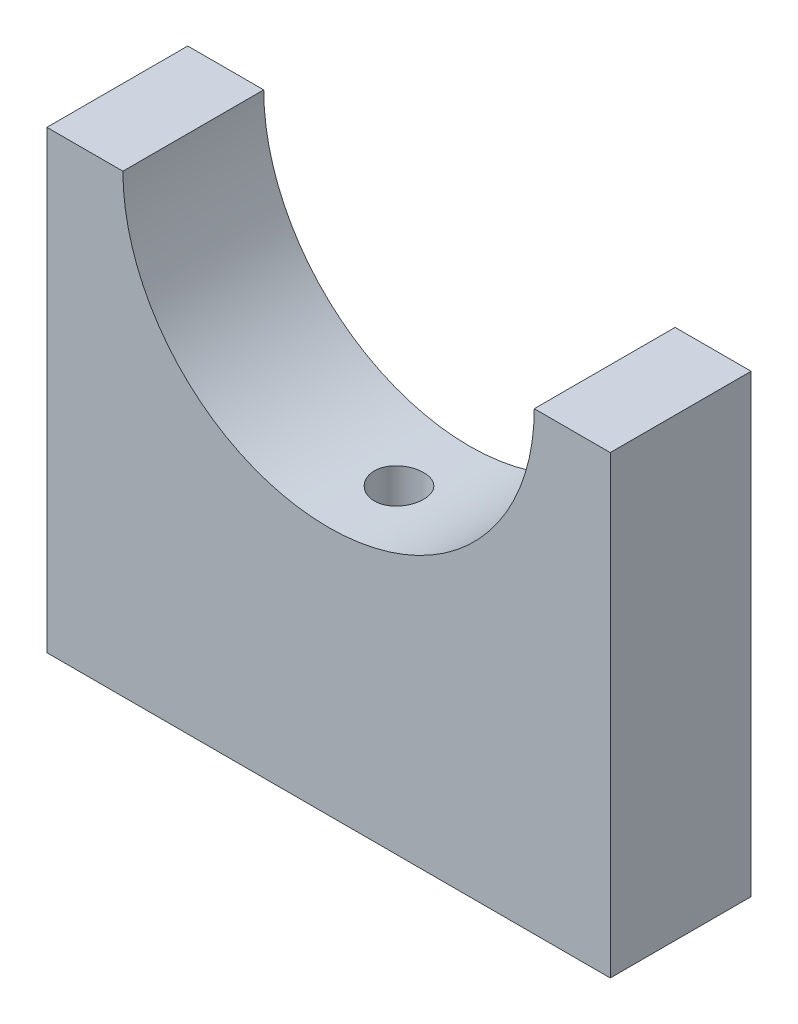
SolidWorks part; units mm, degrees
ref_plane "Front Plane" through (0, 0, 0) normal (0, 0, 1) x (1, 0, 0)
ref_plane "Top Plane" through (0, 0, 0) normal (0, 1, 0) x (1, 0, 0)
ref_plane "Right Plane" through (0, 0, 0) normal (1, 0, 0) x (0, 0, -1)
sketch "Sketch1" plane through (0, 0, 0) normal (0, 0, 1) x (1, 0, 0)
  line L1 (-40, 32.31) -> (40, 32.31)
  line L2 (-40, 32.31) -> (-40, -32.31)
  line L3 (-40, -32.31) -> (40, -32.31)
  line L4 (40, 32.31) -> (40, -32.31)
  line L5 (-40, 32.31) -> (40, -32.31) construction
  line L6 (-40, -32.31) -> (40, 32.31) construction
  point P0 (0, 0)
  dimension "D1" = 64.62
  dimension "D2" = 80
extrude "Boss-Extrude1" add sketch "Sketch1" along normal mid plane 20
sketch "Sketch2" plane through (0, 0, 10) normal (0, 0, 1) x (1, 0, 0)
  line L0 (40, 32.31) -> (-40, 32.31) construction
  line L2 (-29.21, 32.31) -> (29.21, 32.31)
  arc A0 (-29.21, 32.31) -> (29.21, 32.31) centre (0, 32.31) ccw
  point P2 (0, 0)
  point P3 (-18.42, 32.31)
  point P6 (40, 31.1382)
  point P7 (0, 0)
  point P8 (14.21, 32.31)
  point P9 (0, 0)
  point P10 (0, 0)
  point P11 (-16.3099, 32.31)
  point P14 (0, 0)
  point P15 (24.1411, 32.31)
  point P16 (0, 32.31)
  dimension "D1" = 29.21
extrude "Cut-Extrude1" cut sketch "Sketch2" against normal up to surface (20 mm away) up to face at (0, 0, -10)
sketch "Sketch3" plane through (0, -32.31, 0) normal (0, -1, 0) x (1, 0, 0)
  point P0 (0, 0)
hole_wizard "M6 Clearance Hole1" positions "Sketch4" profile "Sketch5" hole size "M6" standard "ANSI Metric" end condition through all
sketch "Sketch4" plane through (0, -32.31, 0) normal (0, -1, 0) x (-1, 0, 0)
  point P0 (0, 0)
sketch "Sketch5" plane through (0, -32.31, 0) normal (1, 0, 0) x (0, 0, -1)
  line L0 (0, 0) -> (0, 64.62)
  line L1 (0, 64.62) -> (3.5, 64.62)
  line L2 (3.5, 64.62) -> (3.5, 0)
  line L5 (3.5, 0) -> (0, 0)
  line L11 (0, -6.35) -> (0, 107.95) construction
  dimension "Thru Hole Dia." = 7
  dimension "Thru Hole Depth" = 64.62
